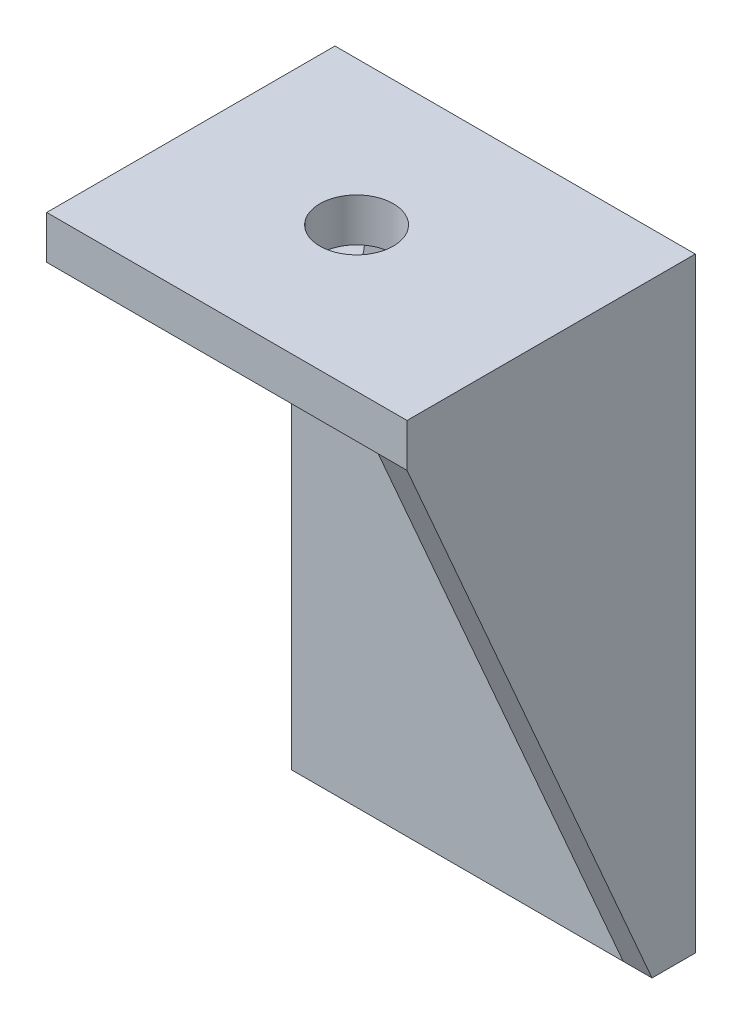
SolidWorks part; units mm, degrees
ref_plane "Front Plane" through (0, 0, 0) normal (0, 0, 1) x (1, 0, 0)
ref_plane "Top Plane" through (0, 0, 0) normal (0, 1, 0) x (1, 0, 0)
ref_plane "Right Plane" through (0, 0, 0) normal (1, 0, 0) x (0, 0, -1)
sketch "Sketch1" plane through (0, 0, 0) normal (0, 0, 1) x (1, 0, 0)
  line L0 (0, 39) -> (23, 39) construction
  line L1 (0, 0) -> (23, 0)
  line L2 (0, 0) -> (0, 42)
  line L3 (0, 42) -> (23, 42)
  line L4 (23, 0) -> (23, 42)
  circle A0 centre (17.34, 12.13) radius 2.05
  circle A1 centre (2.99, 34.1) radius 2.05
  circle A2 centre (17.34, 12.13) radius 3.5 construction
  circle A3 centre (2.99, 34.1) radius 3.5 construction
  dimension "D6" = 4.1
  dimension "D9" = 7
  dimension "D1" = 23
  dimension "D2" = 42
  dimension "D3" = 3
  dimension "D4" = 2.99
  dimension "D5" = 17.34
  dimension "D7" = 34.1
  dimension "D8" = 12.13
extrude "Boss-Extrude1" add sketch "Sketch1" along normal blind 3
sketch "Sketch2" plane through (0, 42, 0) normal (0, 1, 0) x (1, 0, 0)
  line L0 (0, 0) -> (23, 0) construction
  line L1 (0, -3) -> (23, -3)
  line L2 (0, -3) -> (0, -20)
  line L3 (0, -20) -> (23, -20)
  line L4 (23, -3) -> (23, -20)
  line L5 (11.5, -20) -> (11.5, 0) construction
  circle A0 centre (11.5, -10) radius 2.55
  point P11 (11.5, 0)
  dimension "D2" = 5.1
  dimension "D1" = 20
extrude "Boss-Extrude2" add sketch "Sketch2" against normal up to vertex (3 mm away) up to point (0, 39, 0)
sketch "Sketch3" plane through (23, 0, 0) normal (1, 0, 0) x (0, 0, -1)
  line L0 (-20, 39) -> (-3, 0)
  line L1 (-20, 39) -> (-20, 42) construction
  line L2 (-20, 42) -> (0, 42) construction
  line L3 (0, 0) -> (0, 42) construction
  line L4 (-3, 0) -> (0, 0) construction
  line L5 (-20, 39) -> (-20, 42)
  line L6 (-20, 42) -> (0, 42)
  line L7 (0, 0) -> (0, 42)
  line L8 (-3, 0) -> (0, 0)
extrude "Boss-Extrude3" add sketch "Sketch3" along normal blind 2
